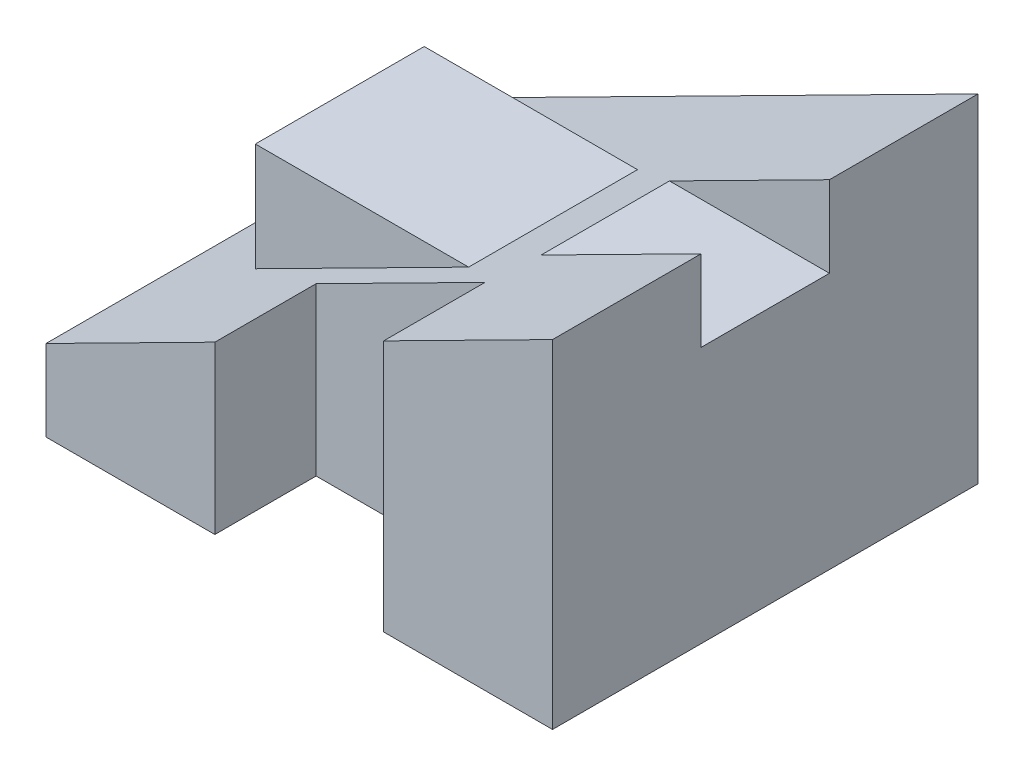
SolidWorks part; units mm, degrees
ref_plane "Front Plane" through (0, 0, 0) normal (0, 0, 1) x (1, 0, 0)
ref_plane "Top Plane" through (0, 0, 0) normal (0, 1, 0) x (1, 0, 0)
ref_plane "Right Plane" through (0, 0, 0) normal (1, 0, 0) x (0, 0, -1)
sketch "Sketch1" plane through (0, 0, 0) normal (0, 0, 1) x (1, 0, 0)
  line L0 (0, 0) -> (75, 0)
  line L1 (75, 0) -> (75, 50)
  line L2 (75, 50) -> (0, 12)
  line L3 (0, 12) -> (0, 0)
  line L4 (25, 24.6667) -> (25, 0)
  line L5 (50, 37.3333) -> (50, 0)
  line L6 (12, 18.08) -> (12, 34.08)
  line L7 (12, 34.08) -> (43.5789, 34.08)
  line L8 (51.3158, 38) -> (75, 38)
  dimension "D1" = 75
  dimension "D2" = 50
  dimension "D3" = 12
  dimension "D4" = 25
  dimension "D5" = 25
  dimension "D6" = 16
  dimension "D7" = 12
  dimension "D8" = 12
extrude "Boss-Extrude2" add sketch "Sketch1" against normal blind 63 contours L4 L2 L3 L0 | L5 L2 L4 L0 | L8 L2 L5 L0 L1 | L2 L8 L1 region at (13.9394, 9.5313, 0) region at (38.3513, 15.7157, 0) region at (62.5056, 18.9913, 0) region at (67.1053, 42, 0)
extrude "Cut-Extrude1" cut sketch "Sketch1<5>" against normal blind 15 contours L5 L2 L4 L0 region at (38.3513, 15.7157, 0)
sketch "Sketch1<5>" plane through (0, 0, 0) normal (0, 0, 1) x (1, 0, 0) same geometry as "Sketch1"
extrude "Boss-Extrude4" add sketch "Sketch1<7>" against normal blind 25 from offset 19 contours L7 L6 L2 region at (22.5263, 28.7467, 0) offset against normal yes
sketch "Sketch1<7>" plane through (0, 0, 0) normal (0, 0, 1) x (1, 0, 0) same geometry as "Sketch1"
extrude "Boss-Extrude5" add sketch "Sketch1<8>" against normal blind 19 from offset 22 contours L2 L8 L1 region at (67.1053, 42, 0) offset against normal yes
sketch "Sketch1<8>" plane through (0, 0, 0) normal (0, 0, 1) x (1, 0, 0) same geometry as "Sketch1"
extrude "Cut-Extrude2" cut sketch "Sketch1<9>" against normal blind 19 from offset 22 contours L2 L8 L1 region at (67.1053, 42, 0) offset against normal yes
sketch "Sketch1<9>" plane through (0, 0, 0) normal (0, 0, 1) x (1, 0, 0) same geometry as "Sketch1"
